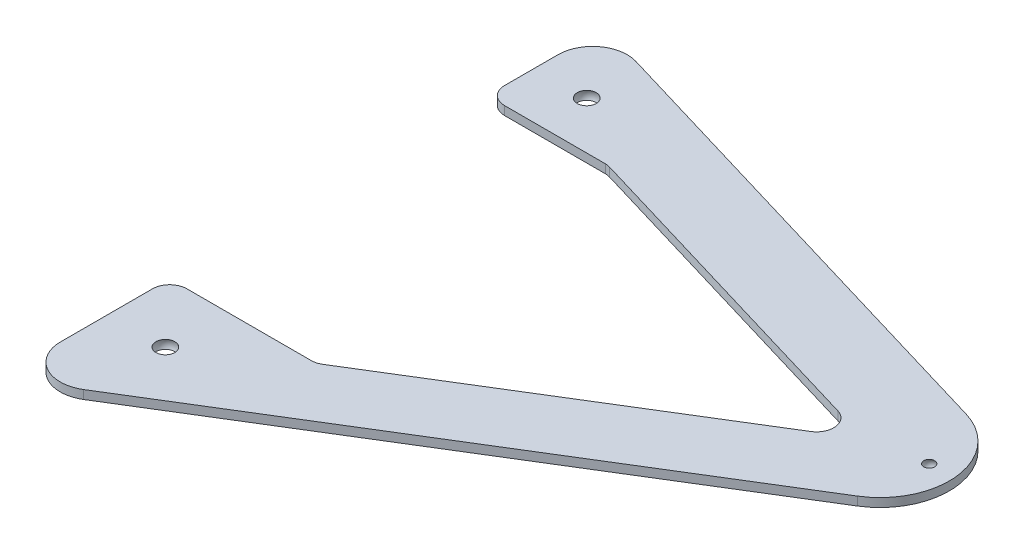
SolidWorks part; units mm, degrees
material "2014-T4"
ref_plane "Piano frontale" through (0, 0, 0) normal (0, 0, 1) x (1, 0, 0)
ref_plane "Piano superiore" through (0, 0, 0) normal (0, 1, 0) x (1, 0, 0)
ref_plane "Piano destro" through (0, 0, 0) normal (1, 0, 0) x (0, 0, -1)
sketch "Schizzo2" plane through (0, 0, 0) normal (0, 1, 0) x (1, 0, 0)
  line L0 (0, 0) -> (0, 350)
  line L1 (0, 350) -> (383.3259, 235.7143)
  line L2 (383.3259, 235.7143) -> (0, 0)
  dimension "D1" = 350
  dimension "D2" = 450
  dimension "D3" = 400
extrude "Estrusione-Estrusione1" add sketch "Schizzo2" along normal blind 5 contours L1 L2 L0
sketch "Schizzo3" plane through (0, 5, 0) normal (0, 1, 0) x (1, 0, 0)
  line L0 (0, 0) -> (0, 350) construction
  line L1 (0, 350) -> (383.3259, 235.7143) construction
  point P0 (30, 309.7508)
  point P1 (311.7446, 225.7508)
  point P2 (32.8765, 63.5676)
  dimension "D1" = 30
  dimension "D2" = 30
  dimension "D3" = 30
  dimension "D4" = 294
  dimension "D5" = 322.6
  dimension "D6" = 246.2
ref_plane "Piano1" through (0, 2.5, 0) normal (0, 1, 0) x (1, 0, 0)
sketch "Schizzo7" plane through (0, 2.5, 0) normal (0, 1, 0) x (1, 0, 0)
  line L0 (311.7446, 229.7508) -> (311.7446, 221.7508)
  arc A0 (311.7446, 221.7508) -> (311.7446, 229.7508) centre (311.7446, 225.7508) ccw
revolve "Rivoluzione4" add sketch "Schizzo7" angle 360 about L0
sketch "Schizzo9" plane through (0, 2.5, 0) normal (0, 1, 0) x (1, 0, 0)
  line L0 (30, 315.7508) -> (30, 303.7508)
  arc A0 (30, 303.7508) -> (30, 315.7508) centre (30, 309.7508) cw
revolve "Rivoluzione5" add sketch "Schizzo9" angle 360 about L0
sketch "Schizzo11" plane through (0, 2.5, 0) normal (0, 1, 0) x (1, 0, 0)
  line L0 (35.0832, 69.1471) -> (30.6699, 57.9881)
  arc A0 (35.0832, 69.1471) -> (30.6699, 57.9881) centre (32.8765, 63.5676) ccw
revolve "Rivoluzione6" add sketch "Schizzo11" angle 360 about L0
combine bodies "Abbina1" operation type subtract main body 101 bodies to subtract 104 102 103
fillet "Raccordo1" radius 20 2 edges at (0, 2.5, 0) (0, 2.5, -350)
fillet "Raccordo2" radius 40 1 edges at (383.3259, 2.5, -235.7143)
sketch "Schizzo12" plane through (0, 5, 0) normal (0, 1, 0) x (1, 0, 0)
  line L0 (69.6395, 282.2801) -> (280.4688, 219.4229)
  line L1 (280.4688, 219.4229) -> (84.5466, 98.9467)
  line L2 (25.7143, 342.3335) -> (297.6117, 261.2693) construction
  line L3 (307.1355, 188.8633) -> (30.4762, 18.7404) construction
  line L4 (84.5466, 98.9467) -> (-35.5023, 98.9467)
  line L5 (-35.5023, 98.9467) -> (-35.5023, 282.2801)
  line L6 (-35.5023, 282.2801) -> (69.6395, 282.2801)
  dimension "D1" = 40
  dimension "D2" = 45
  dimension "D3" = 220
  dimension "D4" = 230
extrude "Taglio-Estrusione1" cut sketch "Schizzo12" against normal through all contours L6 L0 L1 L4 L5
fillet "Raccordo3" radius 10 5 edges at (280.4688, 2.5, -219.4229) (0, 2.5, -98.9467) (84.5466, 2.5, -98.9467) (69.6395, 2.5, -282.2801) (0, 2.5, -282.2801)
